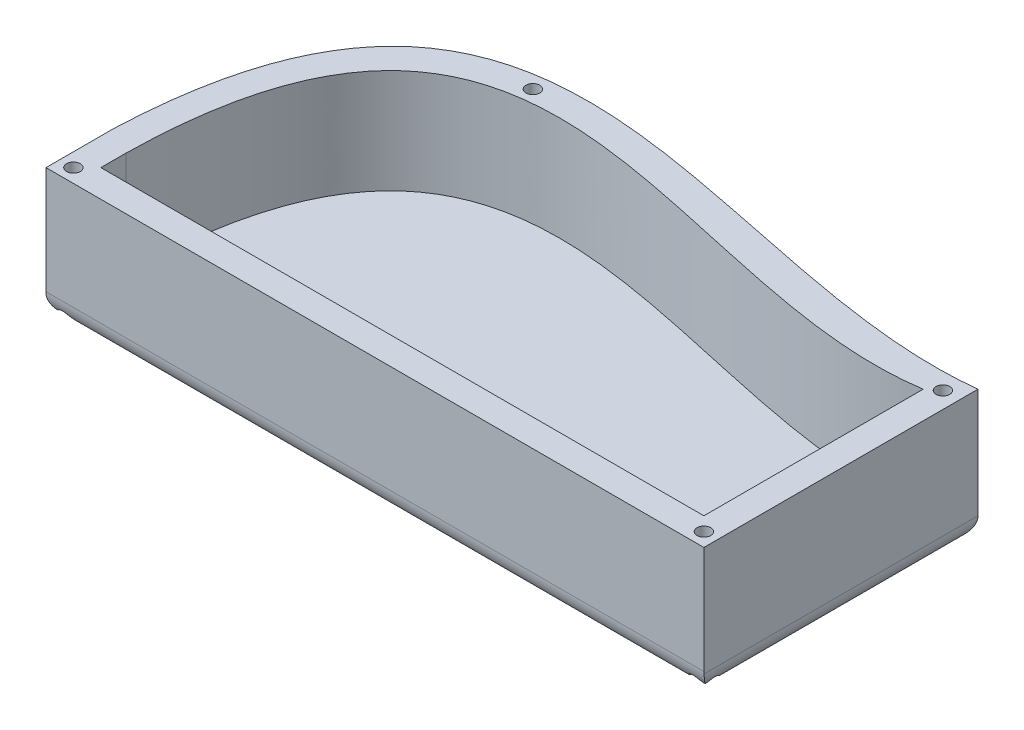
SolidWorks part; units mm, degrees
ref_plane "Front Plane" through (0, 0, 0) normal (0, 0, 1) x (1, 0, 0)
ref_plane "Top Plane" through (0, 0, 0) normal (0, 1, 0) x (1, 0, 0)
ref_plane "Right Plane" through (0, 0, 0) normal (1, 0, 0) x (0, 0, -1)
sketch "Sketch1" plane through (0, 0, 0) normal (0, 1, 0) x (1, 0, 0)
  line L1 (0, 0) -> (76.2, 0)
  line L2 (0, 0) -> (0, 38.1)
  line L3 (0, 38.1) -> (76.2, 38.1)
  line L4 (76.2, 0) -> (76.2, 38.1)
  spline S0 degree 3 poles (0, 0) (-2.1647, 62.6103) (45.4594, 28.2973) (76.2, 31.75) knots 0 0 0 0 1 1 1 1
  dimension "D3" = 18.796
  dimension "D5" = 104.394
  dimension "D1" = 76.2
  dimension "D2" = 38.1
  dimension "D4" = 31.75
  dimension "D6" = 19.304
  dimension "D7" = 33.02
extrude "Boss-Extrude1" add sketch "Sketch1" along normal blind 15.24 contours S0 L2 L1 L4
sketch "Sketch2" plane through (0, 0, 0) normal (0, -1, 0) x (1, 0, 0)
  line L1 (0, 0) -> (76.2, 0)
  line L2 (0, 0) -> (0, -38.1)
  line L3 (0, -38.1) -> (76.2, -38.1)
  line L4 (76.2, 0) -> (76.2, -38.1)
  line L9 (3.175, -3.175) -> (73.025, -3.175)
  line L10 (3.175, -3.175) -> (3.175, -29.8078)
  line L11 (3.175, -29.8078) -> (73.025, -29.8078)
  line L12 (73.025, -3.175) -> (73.025, -29.8078)
  spline S0 degree 3 poles (0, 0) (-2.1647, -62.6103) (45.4594, -28.2973) (76.2, -31.75) knots 0 0 0 0 1 1 1 1
  spline S2 degree 3 poles (3.175, -3.175) (2.3612, -57.3369) (45.979, -24.4463) (73.025, -28.575) knots 0 0 0 0 1 1 1 1
  dimension "D4" = 19.304
  dimension "D6" = 104.394
  dimension "D11" = 25.4
  dimension "D12" = 15.621
  dimension "D14" = 92.8132
  dimension "D1" = 76.2
  dimension "D2" = 38.1
  dimension "D3" = 18.796
  dimension "D5" = 33.02
  dimension "D7" = 31.75
  dimension "D8" = 3.175
  dimension "D9" = 3.175
  dimension "D10" = 3.175
  dimension "D13" = 19.304
  dimension "D15" = 26.67
sketch "Sketch3" plane through (0, 15.24, 0) normal (0, 1, 0) x (1, 0, 0)
  line L0 (0, 0) -> (76.2, 0) construction
  line L1 (73.025, 3.175) -> (3.175, 3.175)
  line L2 (73.025, 3.175) -> (73.025, 29.8078)
  line L3 (73.025, 29.8078) -> (3.175, 29.8078)
  line L4 (3.175, 3.175) -> (3.175, 29.8078)
  spline S0 degree 3 poles (73.025, 28.575) (45.979, 24.4463) (2.3612, 57.3369) (3.175, 3.175) knots 0 0 0 0 1 1 1 1
extrude "Cut-Extrude2" cut sketch "Sketch3" against normal blind 12.065 contours L2 S0 L3 L4 L1 | L3 S0
sketch "Sketch5" plane through (0, 15.24, 0) normal (0, 1, 0) x (1, 0, 0)
  line L0 (0, 0) -> (76.2, 0) construction
  line L1 (0, 0) -> (0, 7.7712) construction
  line L2 (76.2, 0) -> (76.2, 31.75) construction
  circle A0 centre (1.5875, 1.5875) radius 0.7937
  circle A1 centre (74.6125, 1.5875) radius 0.7937
  circle A2 centre (74.295, 29.591) radius 0.7937
  circle A3 centre (20.32, 36.068) radius 0.7937
  dimension "D5" = 1.5875
  dimension "D1" = 1.5875
  dimension "D2" = 1.5875
  dimension "D3" = 1.5875
  dimension "D4" = 1.5875
  dimension "D6" = 1.27
  dimension "D7" = 1.016
  dimension "D8" = 20.32
  dimension "D9" = 36.068
extrude "Cut-Extrude4" cut sketch "Sketch5" against normal through all
sketch "Sketch6" plane through (0, 0, 0) normal (0, -1, 0) x (1, 0, 0)
  circle A1 centre (74.6125, -1.5875) radius 1.27
  circle A2 centre (1.5875, -1.5875) radius 1.27
  circle A3 centre (20.32, -36.068) radius 1.27
  circle A4 centre (74.295, -29.591) radius 1.27
  dimension "D5" = 2.54
extrude "Cut-Extrude5" cut sketch "Sketch6" against normal blind 2.54
fillet "Fillet3" radius 2.54 2 edges at (0, 0, -3.8856)
fillet "Fillet4" radius 2.54 3 edges at (76.2, 0, -14.5975) (76.2, 0.5622, -30.7979)
fillet "Fillet5" radius 2.794 7 edges at (2.8575, 0, -1.5875) (73.3425, 0, -1.5875) (38.1, 0, 0) (0.3195, 1.3068, -1.517) (0.7439, 0.7439, 0) (75.8805, 1.3068, -1.658) (75.4561, 0.7439, 0)
scale "Scale1" scale about centroid uniform scaling yes scale factor 1.5
